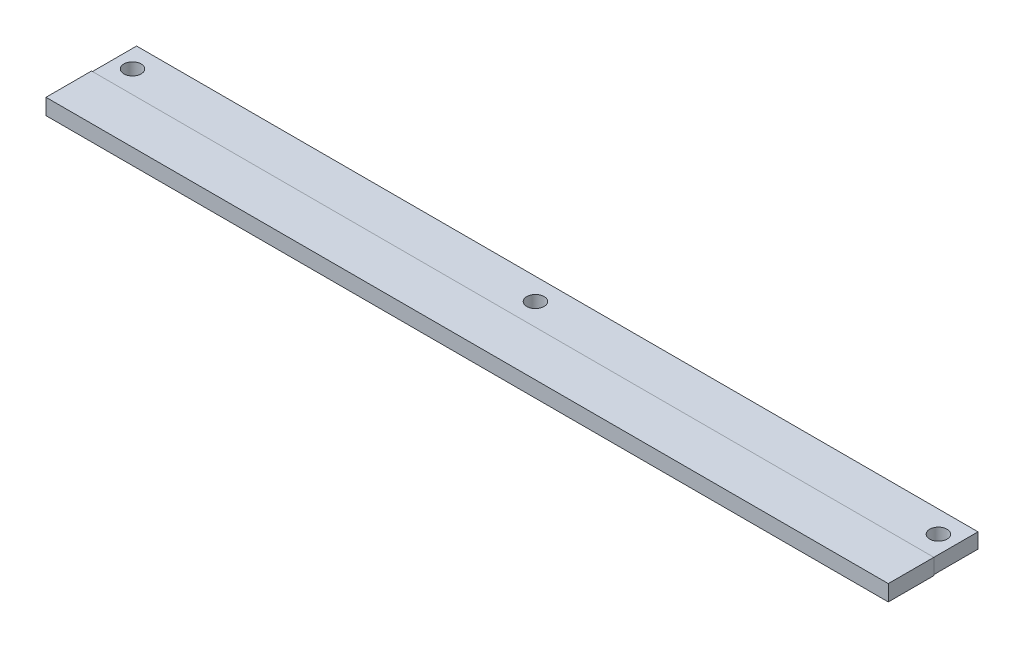
SolidWorks part; units mm, degrees
ref_plane "Front Plane" through (0, 0, 0) normal (1, 0, 0) x (0, 1, 0)
ref_plane "Top Plane" through (0, 0, 0) normal (0, 0, 1) x (0, 1, 0)
ref_plane "Right Plane" through (0, 0, 0) normal (0, 1, 0) x (-1, 0, 0)
sketch "Sketch1" plane through (0, 0, 0) normal (0, 0, 1) x (0, 1, 0)
  line L1 (0, 0) -> (3.5, 0)
  line L2 (0, 0) -> (0, 185)
  line L3 (0, 185) -> (3.5, 185)
  line L4 (3.5, 0) -> (3.5, 185)
  dimension "D1" = 185
  dimension "D2" = 3.5
extrude "Boss-Extrude1" add sketch "Sketch1" along normal blind 20 contours L2 L1 L4 L3
sketch "Sketch2" plane through (0, 3.5, 0) normal (0, 1, 0) x (-1, 0, 0)
  line L1 (185, 0) -> (181, 0)
  line L2 (185, 0) -> (185, 5)
  line L3 (185, 5) -> (181, 5)
  line L4 (181, 0) -> (181, 5)
  circle A0 centre (181, 5) radius 1.9
  dimension "D3" = 3.8
  dimension "D1" = 4
  dimension "D2" = 5
extrude "Cut-Extrude1" cut sketch "Sketch2" against normal up to next contours A0
pattern_linear "LPattern1" count 3 spacing 88.5 along (1, 0, 0) of "Cut-Extrude1"
ref_plane "Plane1" through (0, 0, 10) normal (0, 0, -1) x (-1, 0, 0)
mirror "Mirror1" [suppressed] about plane through (0, 0, 10) normal (0, 0, -1)
sketch "Sketch3" plane through (0, 0, 0) normal (0, 0, -1) x (1, 0, 0)
  line L0 (-184.9, -0.1) -> (-184.9, -3.4)
  line L1 (-185, 0) -> (0, 0)
  line L2 (-185, 0) -> (-185, -3.5)
  line L3 (-185, -3.5) -> (0, -3.5)
  line L4 (0, 0) -> (0, -3.5)
  line L5 (-184.9, -3.4) -> (-0.1, -3.4)
  line L6 (-0.1, -0.1) -> (-0.1, -3.4)
  line L7 (-184.9, -0.1) -> (-0.1, -0.1)
extrude "Cut-Extrude2" cut sketch "Sketch3" against normal blind 10
sketch "Sketch5" plane through (0, 3.4, 0) normal (0, 1, 0) x (-1, 0, 0)
  line L0 (0.1, 10) -> (0.1, 0) construction
  line L1 (184.9, 0) -> (0.1, 0)
  line L2 (184.9, 0) -> (184.9, 0.2)
  line L3 (184.9, 0.2) -> (0.1, 0.2)
  line L4 (0.1, 0) -> (0.1, 0.2)
extrude "Cut-Extrude3" cut sketch "Sketch5" against normal up to next
equation "\"whitekey_cutout_length\"= 101.5"
equation "\"wall_thickness\"=10"
equation "\"base_mount_height\"=40"
equation "\"base_rear_length\"=80"
equation "\"D1@Sketch1\"=\"base_rear_length\"+\"base_front_length\"-\"dowel_recess_offset\"*2"
equation "\"D2@Sketch1\"=\"wall_thickness\"-\"dowel_recess_offset\"*2"
equation "\"dowel_recess_offset\"=3.25"
equation "\"guide_brace_height\"=20"
equation "\"guide_brace_thickness\"=2"
equation "\"dowel_recess_depth\"=10"
equation "\"base_front_length\"=111.5"
equation "\"screw_hole_wall_offset\"=7.25"
equation "\"screw_hole_edge_inset\"=\"dowel_recess_depth\"/2"
equation "\"screw_hole_diameter\"=3.8"
equation "\"screw_head_hole_diameter\"=6.7"
equation "\"screw_nut_hole_side_len\"=3.5"
equation "\"D1@Boss-Extrude1\"=\"dowel_recess_depth\"*2"
equation "\"D2@Sketch2\"=\"screw_hole_edge_inset\""
equation "\"D1@Sketch2\"=\"screw_hole_wall_offset\"-\"dowel_recess_offset\""
equation "\"D3@Sketch2\"=\"screw_hole_diameter\""
equation "\"D3@LPattern1\"=0.5*(\"base_front_length\"+\"base_rear_length\"-\"screw_hole_wall_offset\"*2)"
equation "\"D1@Cut-Extrude2\"=\"dowel_recess_depth\""
equation "\"key_mount_recess_length\"=50"
equation "\"key_mount_recess_height\"=12.5"
equation "\"key_mount_recess_depth\"=1.5"
equation "\"screw_shaft_diameter\"=3.5"
equation "\"switch_board_width\"=30"
equation "\"dowel_insert_tolerance\"=0.1"
equation "\"screw_nut_recess_offset\"=0.35"
equation "\"screw_head_and_nut_recess_depth\"=2.5"
equation "\"switch_board_thickness\"=1.6"
equation "\"switch_board_wall_offset\"=11.5"
equation "\"heatset_insert_hole_diameter\"=4.8"
equation "\"heatset_insert_hole_depth\"=3.8"
equation "\"front_rear_panel_width\"=23.75"
equation "\"front_panel_height\"=24"
equation "\"rod_diameter\"=5"
equation "\"rod_head_diameter\"=8"
equation "\"rod_length_adj\"=0.5"
equation "\"rod_insert_length\"=2.8"
equation "\"switch_black_key_mount_height\"=8"
equation "\"switch_white_key_mount_height\"=3"
equation "\"D1@Sketch3\"=\"dowel_insert_tolerance\""
equation "\"D1@Sketch5\"=\"dowel_insert_tolerance\"*2"
